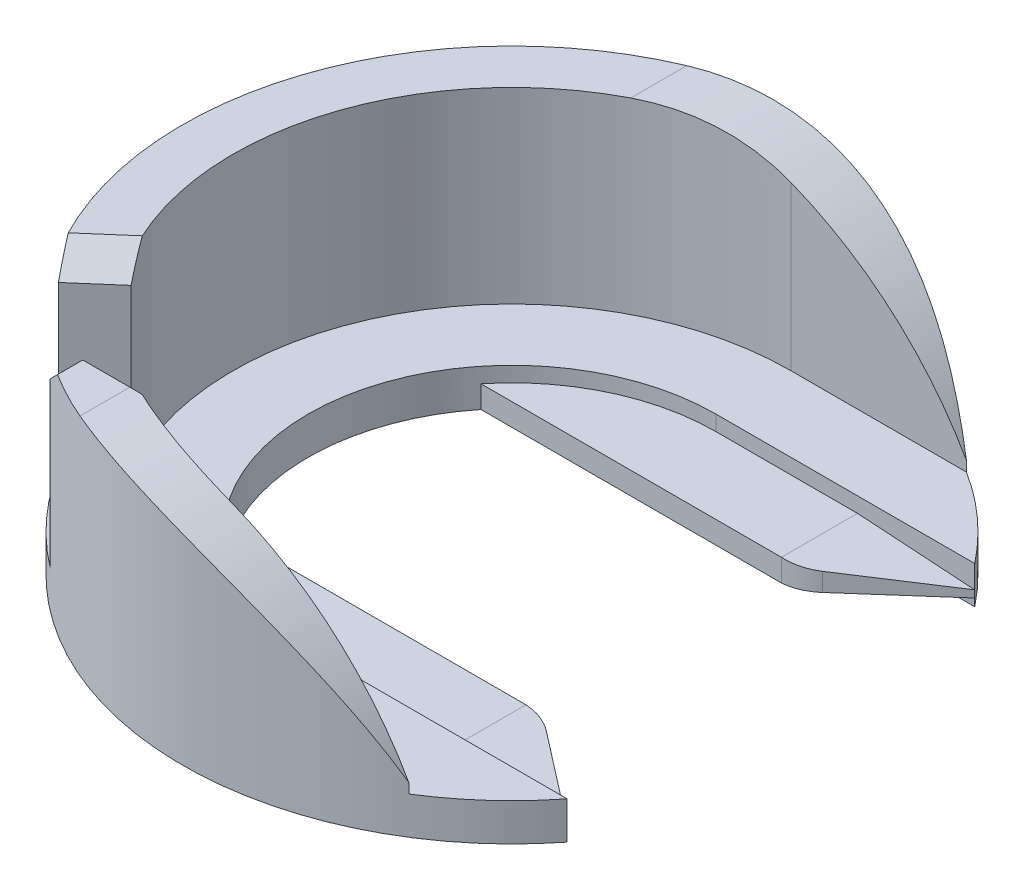
SolidWorks part; units mm, degrees
note: The reader was unsure of these and kept them because the rebuilt part matched: shared geometry of "Sketch1<3>", "Sketch1<4>".
ref_plane "Front Plane" through (0, 0, 0) normal (0, 0, 1) x (1, 0, 0)
ref_plane "Top Plane" through (0, 0, 0) normal (0, 1, 0) x (1, 0, 0)
ref_plane "Right Plane" through (0, 0, 0) normal (1, 0, 0) x (0, 0, -1)
sketch "Sketch1" plane through (0, 0, 0) normal (0, 1, 0) x (1, 0, 0)
  line L0 (-31.3209, 25.2) -> (31.3209, 25.2)
  line L1 (-31.3209, -25.2) -> (31.3209, -25.2)
  line L2 (0, 40.2) -> (51.078, 40.2)
  line L3 (31.3209, 25.2) -> (59.9163, 25.2)
  line L4 (-65, 0) -> (65, 0) construction
  line L5 (31.3209, -25.2) -> (59.9163, -25.2)
  line L6 (0, -40.2) -> (51.078, -40.2)
  line L7 (31.3209, -25.2) -> (51.078, -40.2)
  line L8 (31.3209, 25.2) -> (51.078, 40.2)
  line L9 (0, 55) -> (34.641, 55)
  line L10 (0, -55) -> (34.641, -55)
  circle A0 centre (0, 0) radius 40.2
  circle A1 centre (0, 0) radius 55
  circle A2 centre (0, 0) radius 65
  point P14 (0, 0)
  dimension "D1" = 80.4
  dimension "D3" = 110
  dimension "D4" = 130
  dimension "D2" = 25.2
extrude "Boss-Extrude1" add sketch "Sketch1" along normal blind 4.4 contours A0 L1 | L6 A1 L5 A0 | L4 A2 L6 A1 | L4 A1 L6 A0 | A1 L4 A0 L2 | A2 L4 A1 L2 | L0 A0 | L3 A1 L2 A0 | A1 L8 L2 | A1 L6 L7 | L10 A2 L6 A1 | L2 A2 L9 A1
extrude "Boss-Extrude2" add sketch "Sketch1<3>" along normal blind 40 from surface contours L4 A2 L6 A1 | A2 L4 A1 L2
sketch "Sketch1<3>" plane through (0, 0, 0) normal (0, 1, 0) x (1, 0, 0) same geometry as "Sketch1"
extrude "Boss-Extrude3" add sketch "Sketch1<4>" along normal blind 3 from surface at 4.4 contours A1 L4 A0 L2 | L4 A1 L6 A0 | L10 A2 L6 A1 | L2 A2 L9 A1 starting at face at (10.8827, 4.4, 0)
sketch "Sketch1<4>" plane through (0, 0, 0) normal (0, 1, 0) x (1, 0, 0) same geometry as "Sketch1"
sketch "Sketch2" plane through (0, 44.4, 0) normal (0, 1, 0) x (1, 0, 0)
  line L0 (0, 0) -> (-65, 0) construction
  line L1 (0, 0) -> (-49.0561, -42.6438) construction
  line L2 (-55.3005, -34.1593) -> (-47.6342, -27.4951)
  line L3 (-41.5232, -50.0082) -> (-33.857, -43.344)
  line L4 (-41.5232, -50.0082) -> (-22.8949, -50.0082)
  circle A0 centre (0, 0) radius 65
  circle A1 centre (0, 0) radius 55
  arc M7 (0, -55) -> (0, 55) centre (0, 0) cw
  arc M9 (34.641, 55) -> (34.641, -55) centre (0, 0) ccw
  dimension "D1" = 130
  dimension "D2" = 110
  dimension "D3" = 41
  dimension "D4" = 21
extrude "Cut-Extrude1" cut sketch "Sketch2" against normal up to surface (37 mm away) contours L3 L2 M9 M7 | L3 L4 M7 up to face at (9.6883, 7.4, 0)
sketch "Sketch3" plane through (0, 0, -25.2) normal (0, 0, 1) x (1, 0, 0)
  line L0 (34.641, 44.4) -> (-25.359, 44.4)
  line L2 (34.641, 44.4) -> (34.641, 9.4)
  line L4 (34.641, 44.4) -> (34.641, 7.4) construction
  line L5 (34.641, 44.4) -> (-41.5232, 44.4) construction
  arc A0 (-25.359, 44.4) -> (34.641, 9.4) centre (-25.359, -24.5286) cw
  dimension "D1" = 35
  dimension "D2" = 60
extrude "Cut-Extrude2" cut sketch "Sketch3" against normal through all both and the other way through all
fillet "Fillet1" radius 10 2 edges at (31.3209, 2.2, 25.2) (31.3209, 2.2, -25.2)
sketch "Sketch4" plane through (0, 0, -25.2) normal (0, 0, 1) x (1, 0, 0)
  line L0 (27.9549, 4.4) -> (51.078, 2.9)
  line L1 (51.078, 4.4) -> (51.078, 0) construction
  line L2 (51.078, 2.9) -> (51.078, 1.5)
  line L3 (51.078, 1.5) -> (27.9549, 0)
  line L4 (27.9549, 0) -> (51.078, 0)
  line L5 (51.078, 0) -> (51.078, 4.4)
  line L6 (51.078, 4.4) -> (27.9549, 4.4)
  dimension "D1" = 1.5
  dimension "D2" = 1.5
extrude "Cut-Extrude3" cut sketch "Sketch4" against normal up to surface and the other way up to surface contours L5 L6 L0 | L4 L5 L3 up to face at (25.539, 5.9, -40.2) other way up to face at (25.539, 5.9, 40.2)
fillet "Fillet2" radius 1 1 edges at (-41.5232, 25.9, 50.0082)
chamfer "Chamfer1" distance 5 angle 45 1 edges at (-51.4673, 44.4, 30.8272)
sketch "Sketch5" plane through (0, 0, 50.0082) normal (0, 0, -1) x (-1, 0, 0)
  line L0 (34.6544, 44.4) -> (39.6544, 39.4)
  line L1 (65, 44.4) -> (25.359, 44.4) construction
  line L2 (39.6544, 7.4) -> (39.6544, 44.4) construction
  line L3 (39.6544, 39.4) -> (39.6544, 44.4)
  line L4 (39.6544, 44.4) -> (34.6544, 44.4)
  dimension "D1" = 5
  dimension "D2" = 5
extrude "Cut-Extrude4" cut sketch "Sketch5" against normal up to next
